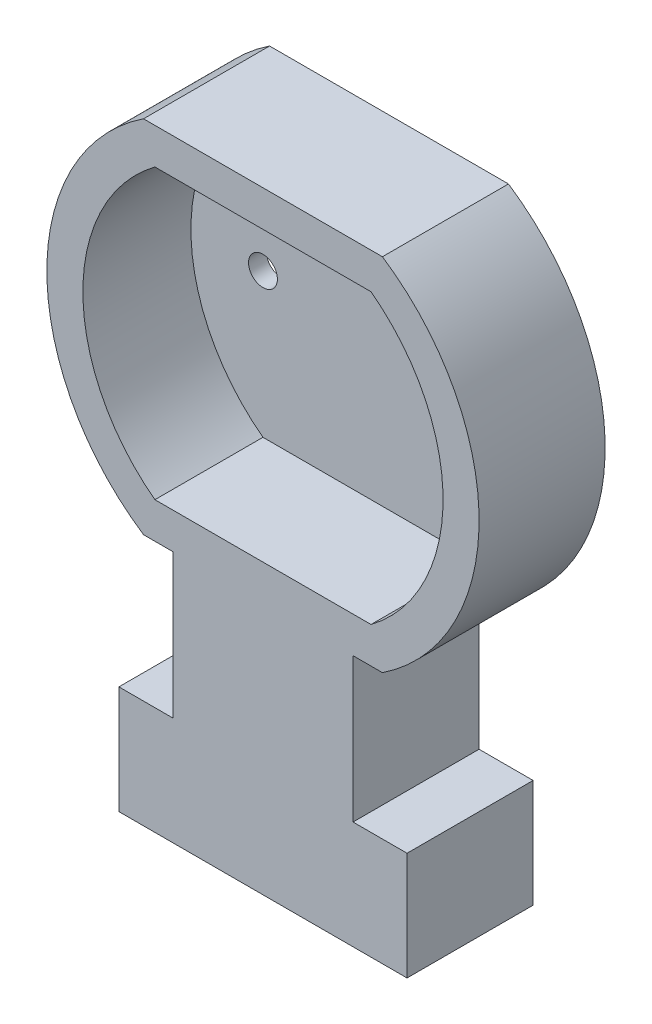
SolidWorks part; units mm, degrees
ref_plane "Plan de face" through (0, 0, 0) normal (0, 0, 1) x (1, 0, 0)
ref_plane "Plan de dessus" through (0, 0, 0) normal (0, 1, 0) x (1, 0, 0)
ref_plane "Plan de droite" through (0, 0, 0) normal (1, 0, 0) x (0, 0, -1)
sketch "Esquisse1" plane through (0, 0, 0) normal (0, 0, 1) x (1, 0, 0)
  line L0 (-3, 4) -> (3, 4)
  line L1 (-3.8932, 0) -> (4.2167, 0) construction
  line L2 (-3, -4) -> (3, -4)
  line L3 (0, 2.9826) -> (0, -7.194) construction
  line L4 (-3.3166, 5) -> (3.3166, 5)
  line L5 (-3.3166, -5) -> (3.3166, -5)
  line L6 (-2.5, -5) -> (-2.5, -9)
  line L7 (-2.5, -9) -> (-4, -9)
  line L8 (-4, -9) -> (-4, -12)
  line L9 (-4, -12) -> (4, -12)
  line L10 (4, -9) -> (4, -12)
  line L11 (2.5, -9) -> (4, -9)
  line L12 (2.5, -5) -> (2.5, -9)
  arc A0 (-3, 4) -> (-3, -4) centre (0, 0) ccw
  arc A2 (3, -4) -> (3, 4) centre (0, 0) ccw
  circle A3 centre (-3, 0) radius 0.4
  circle A4 centre (3, 0) radius 0.4
  arc A5 (3.3166, -5) -> (3.3166, 5) centre (0, 0) ccw
  arc A6 (-3.3166, 5) -> (-3.3166, -5) centre (0, 0) ccw
  point P22 (4, -10.5)
  point P26 (-4, -10.5)
  point P28 (0, -12)
  dimension "D1" = 5
  dimension "D2" = 1
  dimension "D6" = 0.8
  dimension "D3" = 6
  dimension "D4" = 4
  dimension "D5" = 3
  dimension "D7" = 2.5
  dimension "D8" = 4
  dimension "D9" = 4
  dimension "D10" = 3
extrude "Boss.-Extru.1" add sketch "Esquisse1" against normal blind 0.5 contours A6 L5 A5 L4
extrude "Boss.-Extru.2" add sketch "Esquisse1<3>" along normal blind 3 contours A2 L2 A0 L0 region at (0, 4.8438, 0)
sketch "Esquisse1<3>" plane through (0, 0, 0) normal (0, 0, 1) x (1, 0, 0) same geometry as "Esquisse1"
extrude "Enlèv. mat.-Extru.1" cut sketch "Esquisse1<4>" against normal through all contours A3 | A4
sketch "Esquisse1<4>" plane through (0, 0, 0) normal (0, 0, 1) x (1, 0, 0) same geometry as "Esquisse1"
extrude "Boss.-Extru.3" add sketch "Esquisse1<5>" along normal blind 3 and the other way blind 0.5 contours L12 L5 L6 L7 L8 L9 L10 L11 region at (0, -8.9091, 0)
sketch "Esquisse1<5>" plane through (0, 0, 0) normal (0, 0, 1) x (1, 0, 0) same geometry as "Esquisse1"
